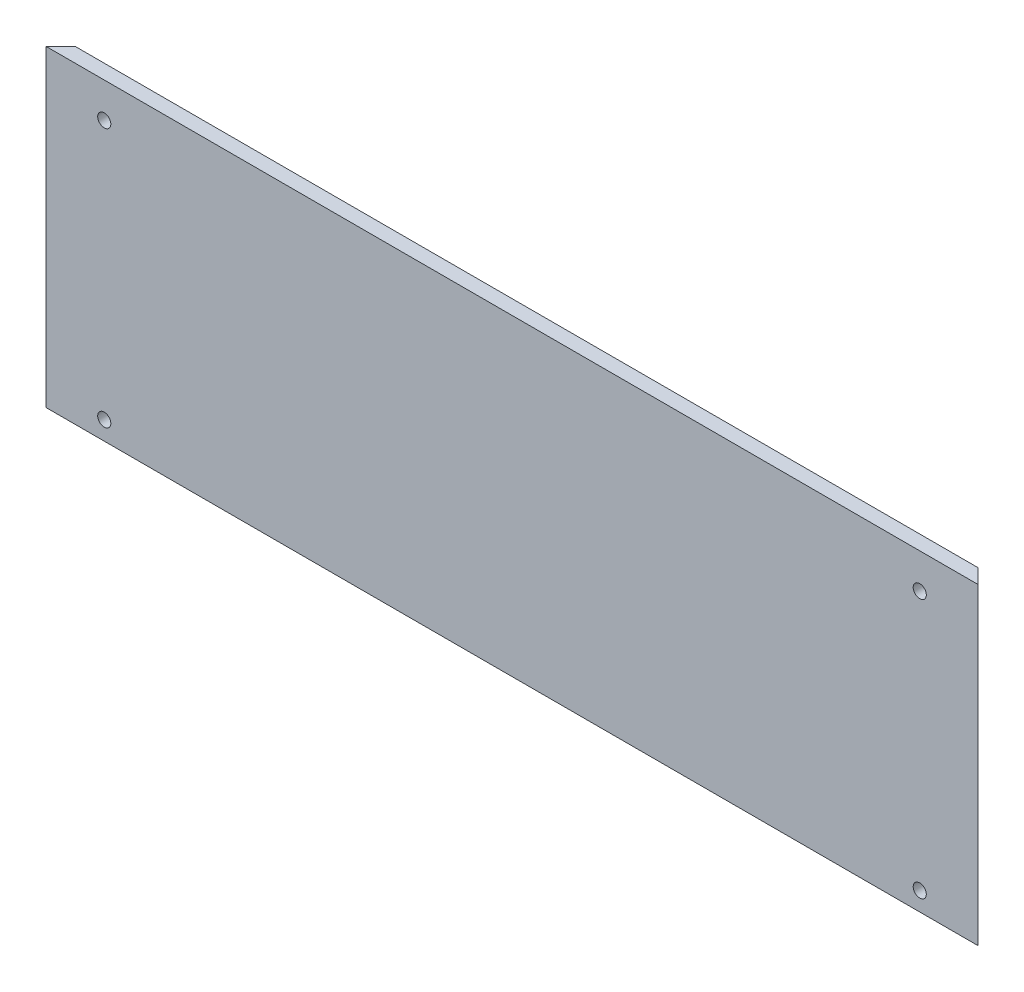
SolidWorks part; units mm, degrees
ref_plane "Front Plane" through (0, 0, 0) normal (0, 0, 1) x (1, 0, 0)
ref_plane "Top Plane" through (0, 0, 0) normal (0, 1, 0) x (1, 0, 0)
ref_plane "Right Plane" through (0, 0, 0) normal (1, 0, 0) x (0, 0, -1)
sketch "Sketch1" plane through (0, 0, 0) normal (0, 0, 1) x (1, 0, 0)
  line L0 (160, 110) -> (160, -37.3998) construction
  line L1 (0, 0) -> (320, 0)
  line L2 (0, 0) -> (0, 110)
  line L3 (0, 110) -> (320, 110)
  line L4 (320, 0) -> (320, 110)
  line L5 (0, 55) -> (320, 55) construction
  circle A0 centre (20, 9) radius 2.25
  circle A1 centre (300, 9) radius 2.25
  circle A4 centre (20, 98) radius 2.25
  circle A5 centre (300, 98) radius 2.25
  dimension "D3" = 20
  dimension "D5" = 4.5
  dimension "D1" = 110
  dimension "D2" = 320
  dimension "D4" = 9
  dimension "D6" = 2
  dimension "D7" = 12
extrude "Boss-Extrude1" add sketch "Sketch1" against normal blind 5
sketch "Sketch2" plane through (0, 0, -5) normal (0, 0, -1) x (-1, 0, 0)
  line L0 (0, 0) -> (-320, 0) construction
  line L1 (0, 0) -> (-320, 0) construction
  line L2 (0, 5) -> (-320, 5)
  line L3 (-320, 5) -> (-320, 110)
  line L4 (-320, 110) -> (0, 110)
  line L5 (0, 110) -> (0, 5)
  circle A1 centre (-20, 9) radius 2.25 construction
  circle A2 centre (-300, 9) radius 2.25 construction
  circle A5 centre (-20, 9) radius 2.25
  circle A6 centre (-300, 9) radius 2.25
  circle A8 centre (-20, 98) radius 2.25 construction
  circle A9 centre (-300, 98) radius 2.25 construction
  circle A10 centre (-20, 98) radius 2.25
  circle A11 centre (-300, 98) radius 2.25
  dimension "D1" = 5
extrude "Boss-Extrude2" add sketch "Sketch2" along normal blind 3
chamfer "Chamfer1" distance 8 angle 45 3 edges at (320, 57.5, -8) (0, 57.5, -8) (160, 110, -8)
chamfer "Chamfer3" distance 3 angle 45 1 edges at (160, 110, -8)
sketch "Sketch3" plane through (160, 0, -160) normal (0.7071, 0, -0.7071) x (-0.7071, 0, -0.7071)
  line L0 (-226.2742, 0) -> (-226.2742, 2.6)
  line L1 (-226.2742, 0) -> (-226.2742, 110) construction
  line L2 (-226.2742, 2.6) -> (-219.2031, 2.6)
  line L4 (-219.2031, 2.6) -> (-219.2031, 0)
  line L5 (-219.2031, 0) -> (-226.2742, 0)
  line L6 (-214.9605, 5) -> (-219.2031, 5) construction
  dimension "D1" = 2.4
extrude "Cut-Extrude1" cut sketch "Sketch3" along direction (1, 0, 0) on the side against the normal through all
